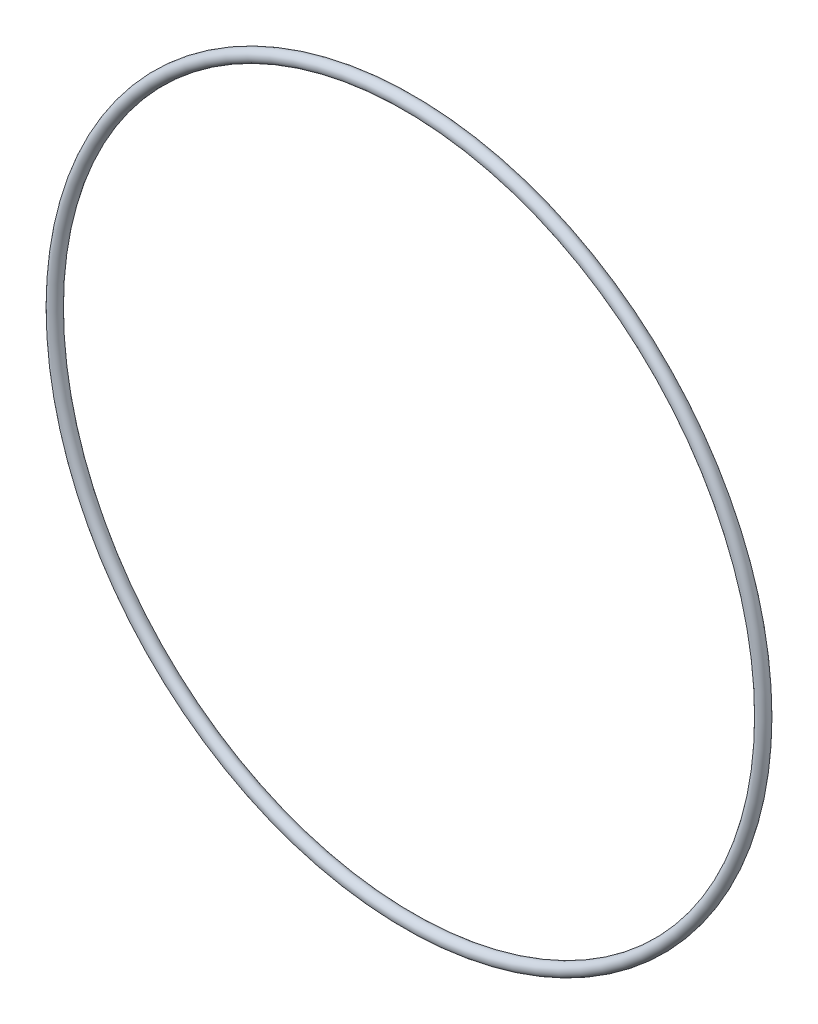
SolidWorks part; units mm, degrees
material "NBR"
ref_plane "前基準面" through (0, 0, 0) normal (0, 0, 1) x (1, 0, 0)
ref_plane "上基準面" through (0, 0, 0) normal (0, 1, 0) x (1, 0, 0)
ref_plane "右基準面" through (0, 0, 0) normal (1, 0, 0) x (0, 0, -1)
sketch "Sketch1" plane through (0, 0, 0) normal (0, 0, 1) x (1, 0, 0)
  circle A0 centre (0, 0) radius 85
  dimension "D1" = 170
sketch "Sketch2" plane through (0, 0, 0) normal (0, 1, 0) x (1, 0, 0)
  circle A0 centre (-86.5, 0) radius 1.5
  point P2 (-89.0055, 0)
  point P4 (0, 0)
  dimension "D1" = 3
  dimension "D2" = 86.5
ref_axis "Axis2" through (0, 0, -1.65) along (0, 0, 1)
revolve "Revolve1" add sketch "Sketch2" angle 360 about axis through (0, 0, -1.65) along (0, 0, 1)
